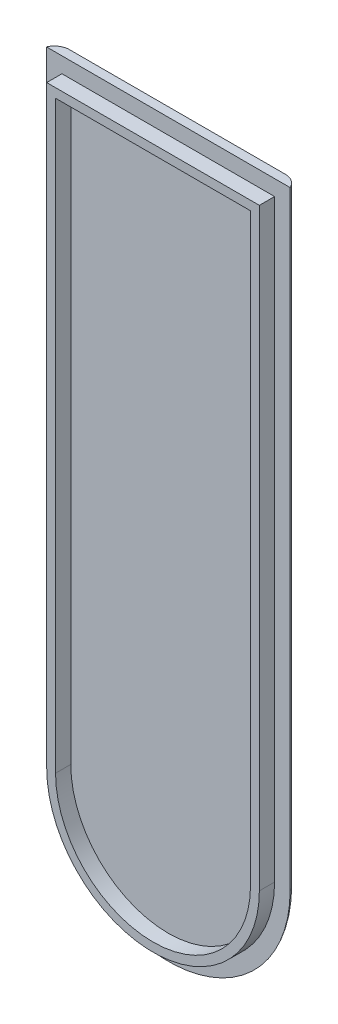
SolidWorks part; units mm, degrees
ref_plane "Plano frontal" through (0, 0, 0) normal (0, 0, 1) x (1, 0, 0)
ref_plane "Plano superior" through (0, 0, 0) normal (0, 1, 0) x (1, 0, 0)
ref_plane "Plano direito" through (0, 0, 0) normal (1, 0, 0) x (0, 0, -1)
sketch "Esboço1" plane through (0, 0, 0) normal (0, 0, 1) x (1, 0, 0)
  line L0 (-40, 0) -> (-40, 200)
  line L1 (-40, 200) -> (40, 200)
  line L2 (40, 200) -> (40, 0)
  arc A0 (-40, 0) -> (40, 0) centre (0, 0) ccw
  dimension "D1" = 80
  dimension "D2" = 200
extrude "Ressalto-extrusão1" add sketch "Esboço1" along normal blind 3
sketch "Esboço2" plane through (0, 0, 3) normal (0, 0, 1) x (1, 0, 0)
  line L0 (-34.9, 0) -> (-34.9, 194.9)
  line L1 (-34.9, 194.9) -> (34.9, 194.9)
  line L2 (34.9, 194.9) -> (34.9, 0)
  line L3 (40, 200) -> (-40, 200) construction
  line L4 (32, 0) -> (32, 191.9)
  line L5 (32, 191.9) -> (-32, 191.9)
  line L6 (-32, 191.9) -> (-32, 0)
  arc A0 (-34.9, 0) -> (34.9, 0) centre (0, 0) ccw
  arc A6 (-32, 0) -> (32, 0) centre (0, 0) ccw
  dimension "D1" = 69.8
  dimension "D3" = 64
  dimension "D2" = 5.1
  dimension "D4" = 3
extrude "Ressalto-extrusão2" add sketch "Esboço2" along normal blind 5
fillet "Filete1" radius 5 3 edges at (40, 100, 0) (0, -40, 0) (-40, 100, 0)
